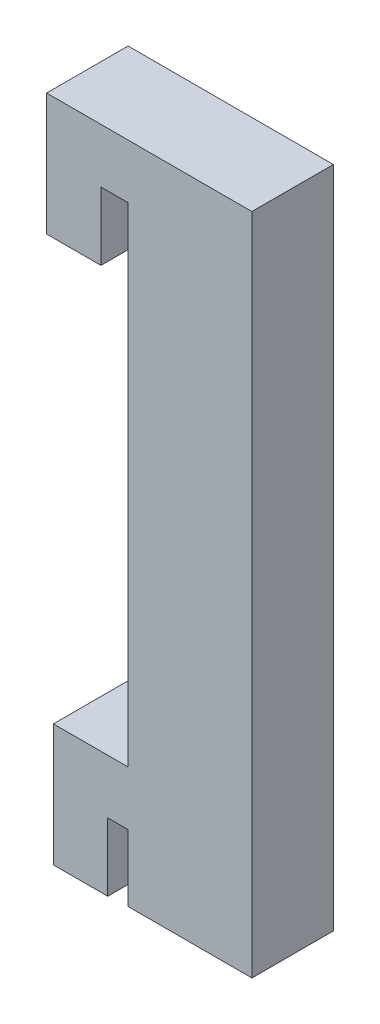
SolidWorks part; units mm, degrees
ref_plane "Plan de face" through (0, 0, 0) normal (0, 0, 1) x (1, 0, 0)
ref_plane "Plan de dessus" through (0, 0, 0) normal (0, 1, 0) x (1, 0, 0)
ref_plane "Plan de droite" through (0, 0, 0) normal (1, 0, 0) x (0, 0, -1)
sketch "Esquisse1" plane through (0, 0, 0) normal (0, 0, 1) x (1, 0, 0)
  line L0 (0, 0) -> (0, 5)
  line L1 (0, 5) -> (1.5, 5)
  line L4 (1.5, 0.0964) -> (10.6219, 0.0964)
  line L5 (10.6219, 0.0964) -> (10.6219, 49)
  line L8 (10.6219, 49) -> (-4.5, 49)
  line L9 (1.5, 45) -> (-0.5, 45)
  line L10 (0, 0) -> (-4, 0)
  line L11 (-4, 0) -> (-4, 9)
  line L12 (-4, 9) -> (1.5, 9)
  line L13 (1.5, 9) -> (1.5, 45)
  line L14 (-0.5, 45) -> (-0.5, 40)
  line L15 (-0.5, 40) -> (-4.5, 40)
  line L16 (-4.5, 40) -> (-4.5, 49)
  line L17 (1.5, 5) -> (1.5, 0.0964)
  point P11 (0.75, 5)
  dimension "D1" = 40
  dimension "D2" = 1.5
  dimension "D3" = 2
  dimension "D4" = 9
  dimension "D5" = 9
  dimension "D6" = 4
  dimension "D7" = 4
  dimension "D8" = 4
  dimension "D9" = 4
extrude "Boss.-Extru.1" add sketch "Esquisse1" along normal blind 6
